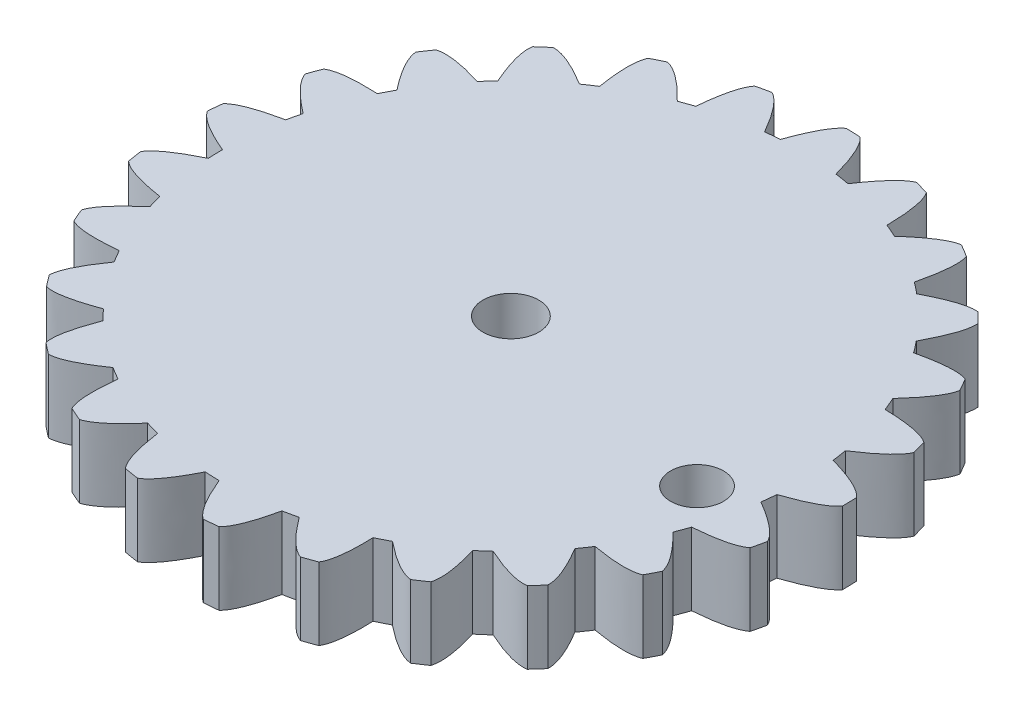
SolidWorks part; units mm, degrees
material "ABS"
ref_plane "Front Plane" through (0, 0, 0) normal (0, 0, 1) x (1, 0, 0)
ref_plane "Top Plane" through (0, 0, 0) normal (0, 1, 0) x (1, 0, 0)
ref_plane "Right Plane" through (0, 0, 0) normal (1, 0, 0) x (0, 0, -1)
sketch "Sketch1" plane through (0, 0, 0) normal (0, 1, 0) x (1, 0, 0)
  line L0 (12.6729, 15.3357) -> (15.4803, 12.4958) construction
  line L2 (14.0766, 13.9158) -> (16.2101, 16.0249) construction
  line L3 (16.2101, 16.0249) -> (16.3487, 16.1619)
  circle A0 centre (0, 0) radius 19.8944
  circle A1 centre (0, 0) radius 22.7939
  spline S0 degree 2 poles (15.4803, 12.4958) (18.6207, 18.4079) (12.6729, 15.3357) knots 0 0 0 1 1 1
  point P3 (12.6729, 15.3357)
  point P4 (15.4803, 12.4958)
  point P6 (15.8547, 16.3766)
  point P12 (11.8864, 15.9531)
  point P14 (16.3487, 16.1619)
  point P15 (16.5577, 15.6654)
  point P16 (8.4094, 18.0296)
  dimension "D1" = 39.7887
  dimension "D4" = 3
  dimension "D5" = 1
  dimension "D2" = 4
  dimension "D3" = 1
extrude "Boss-Extrude4" add sketch "Sketch1" along normal blind 5 contours A0 | A0 S0 A1 region at (14.994, 0, -14.8226) region at (0, 0, 0)
pattern_circular "CirPattern6" count 25 every 14.4 about axis through (0, 5, 0) along (0, 1, 0) of "Boss-Extrude4"
sketch "Sketch2" plane through (0, 5, 0) normal (0, 1, 0) x (1, 0, 0)
  circle A0 centre (0, 0) radius 1.925
  dimension "D1" = 3.85
extrude "Cut-Extrude2" cut sketch "Sketch2" against normal blind 10 contours A0 region at (0, 5, 0)
sketch "Sketch4" plane through (0, 0, 0) normal (0, -1, 0) x (1, 0, 0)
  circle A0 centre (16.5841, 3.7373) radius 1.825
  dimension "D1" = 17
  dimension "D2" = 3.65
extrude "Cut-Extrude3" cut sketch "Sketch4" against normal blind 10
equation "\"number-of-teeth\"= 25"
equation "\"gear-size\"= 4mm"
equation "\"circumference\"= \"number-of-teeth\" * ( ( 1 + \"space-between-teeth\" ) * \"gear-size\" )"
equation "\"space-between-teeth\"= .25"
equation "\"D1@Sketch1\" = \"circumference\" / pi"
equation "\"D2@Sketch1\"=\"gear-size\""
equation "\"gear-length\"= 3mm"
equation "\"D4@Sketch1\"=\"gear-length\""
equation "\"D5@Sketch1\"=\"gear-size\" * \"space-between-teeth\""
equation "\"D3@Sketch1\"=\"gear-size\" * \"space-between-teeth\""
equation "\"D1@CirPattern6\"=\"number-of-teeth\""
equation "\"D2@CirPattern6\"=360 / \"number-of-teeth\""
